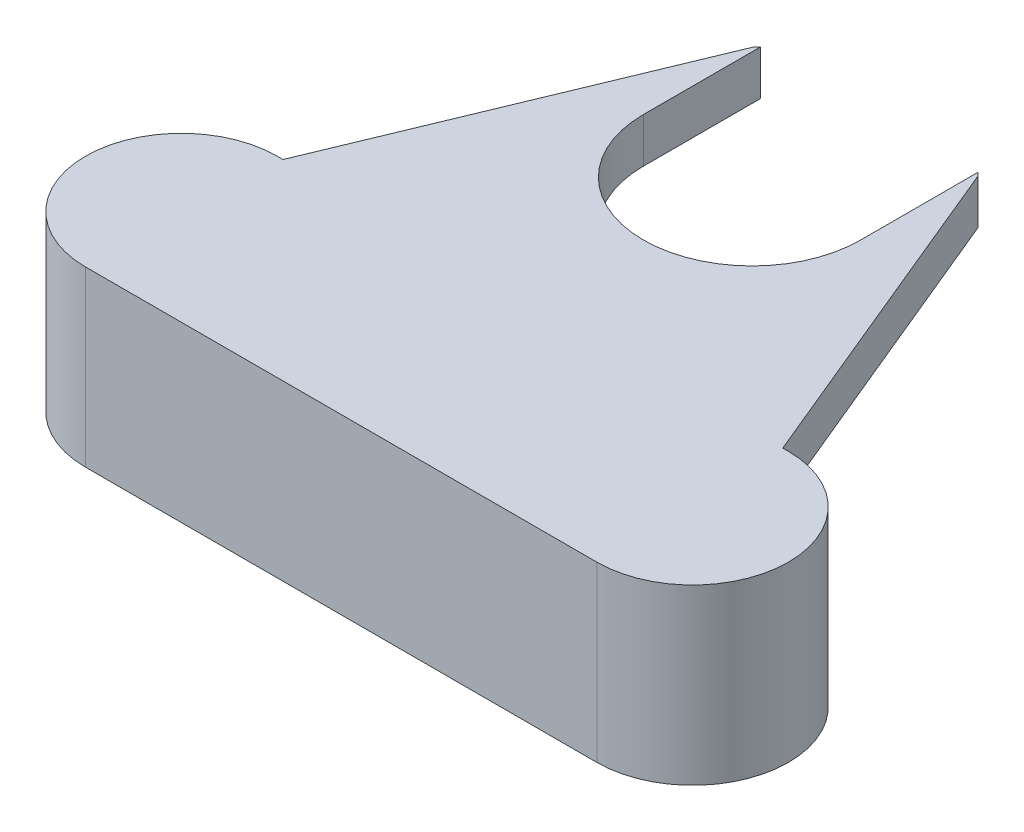
SolidWorks part; units mm, degrees
ref_plane "Front Plane" through (0, 0, 0) normal (0, 0, 1) x (1, 0, 0)
ref_plane "Top Plane" through (0, 0, 0) normal (0, 1, 0) x (1, 0, 0)
ref_plane "Right Plane" through (0, 0, 0) normal (1, 0, 0) x (0, 0, -1)
sketch "Sketch1" plane through (0, 0, 0) normal (0, 1, 0) x (1, 0, 0)
  line L0 (-20, 0) -> (20, 0) construction
  line L1 (-20, 7.5) -> (20, 7.5)
  line L2 (20, -7.5) -> (-20, -7.5)
  circle A0 centre (20, 0) radius 7.5
  circle A1 centre (-20, 0) radius 7.5
  point P4 (0, 0)
  dimension "D1" = 40
  dimension "D2" = 15
extrude "Boss-Extrude1" add sketch "Sketch1" along normal blind 13.57 contours A0 | A1 A0 L1 | A1 L2 A0 | A1 region at (0, 0, 0) region at (-20, 0, 0) region at (20, 0, 0)
ref_plane "Plane1" through (0, 13.57, 0) normal (0, -1, 0) x (-1, 0, 0)
sketch "Sketch3" plane through (0, 13.57, 0) normal (0, -1, 0) x (-1, 0, 0)
  line L0 (0, 0) -> (0, 21.3454) construction
  line L1 (0, 10) -> (0, 7.5) construction
  line L2 (29.0391, 7.5) -> (-29.0391, 7.5)
  line L3 (23.9129, -0.4221) -> (0, 57.3087) construction
  line L4 (-35.3553, 24.6447) -> (35.3553, 24.6447) construction
  line L5 (-35.3553, 24.6447) -> (-35.3553, 95.3553) construction
  line L6 (-35.3553, 95.3553) -> (35.3553, 95.3553) construction
  line L7 (35.3553, 24.6447) -> (35.3553, 95.3553) construction
  line L8 (-35.3553, 24.6447) -> (35.3553, 95.3553) construction
  line L9 (-35.3553, 95.3553) -> (35.3553, 24.6447) construction
  line L10 (0, 57.3087) -> (-24.0511, -0.7557) construction
  line L11 (-8.5, 24.6447) -> (-8.5, 33.8098)
  line L12 (8.5, 24.6447) -> (8.5, 33.8098)
  line L13 (22.989, -0.8048) -> (0, 54.6956)
  line L14 (0, 54.6956) -> (-23.1272, -1.1384)
  circle A0 centre (0, 60) radius 50 construction
  circle A1 centre (0, 24.6447) radius 7.5 construction
  circle A2 centre (0, 24.6447) radius 12.5
  circle A3 centre (0, 24.6447) radius 8.5
  point P2 (0, 10)
  point P4 (0, 10)
  point P27 (18.1786, 13.4217)
  point P28 (-18.1786, 13.4217)
  point P33 (0, 7.5)
  dimension "D2" = 100
  dimension "D3" = 5
  dimension "D5" = 15
  dimension "D4" = 45
  dimension "D6" = 1
  dimension "D7" = 1
extrude "Boss-Extrude3" add sketch "Sketch3" along normal blind 3.5 contours A2 L14 L2 L13 | A3 L11 A2 L14 L13 L12 region at (0, 13.57, -7.9264) region at (0, 13.57, -12.4755)
